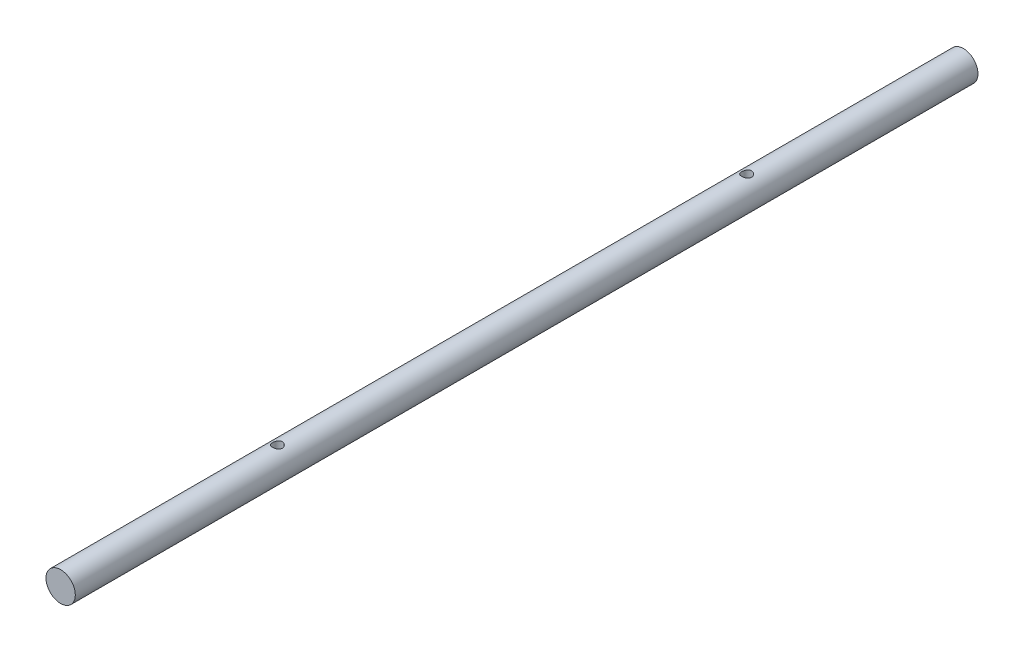
SolidWorks part; units mm, degrees
material "Plain Carbon Steel"
ref_plane "Front Plane" through (0, 0, 0) normal (0, 0, 1) x (1, 0, 0)
ref_plane "Top Plane" through (0, 0, 0) normal (0, 1, 0) x (1, 0, 0)
ref_plane "Right Plane" through (0, 0, 0) normal (1, 0, 0) x (0, 0, -1)
sketch "Sketch1" plane through (0, 0, 0) normal (0, 0, 1) x (1, 0, 0)
  circle A0 centre (0, 0) radius 9.525
  dimension "D1" = 19.05
extrude "Boss-Extrude1" add sketch "Sketch1" along normal blind 586.105
sketch3d "3DSketch1" plane through (0, 0, 0) normal (0, 0, 1) x (1, 0, 0)
ref_axis "Axis1" through (0, 0, 586.105) along (0, 0, -1)
ref_plane "Plane1" through (0, -9.525, 0) normal (0, 1, 0) x (1, 0, 0)
sketch "Sketch3" plane through (0, -9.525, 0) normal (0, 1, 0) x (1, 0, 0)
  line L0 (0, -586.105) -> (0, 0) construction
  line L1 (9.525, 0) -> (-9.525, 0) construction
  line L2 (-9.525, -586.105) -> (9.525, -586.105) construction
  circle A0 centre (0, -445.389) radius 3.175
  circle A1 centre (0, -140.716) radius 3.175
  dimension "D1" = 0
  dimension "D2" = 0
  dimension "D3" = 6.35
  dimension "D4" = 140.716
  dimension "D5" = 6.35
  dimension "D6" = 140.716
extrude "Cut-Extrude2" cut sketch "Sketch3" along normal up to next
sketch "Sketch5" plane through (0, -9.525, 0) normal (0, 1, 0) x (1, 0, 0)
  line L0 (0, -178.816) -> (0, -159.766) construction
  line L1 (-2.3813, -178.816) -> (-2.3813, -159.766)
  line L2 (2.3813, -178.816) -> (2.3813, -159.766)
  line L3 (0, -407.289) -> (0, -426.339) construction
  line L4 (2.3812, -407.289) -> (2.3812, -426.339)
  line L5 (-2.3813, -407.289) -> (-2.3813, -426.339)
  arc A0 (-2.3813, -178.816) -> (2.3813, -178.816) centre (0, -178.816) ccw
  arc A1 (2.3813, -159.766) -> (-2.3813, -159.766) centre (0, -159.766) ccw
  arc A2 (2.3812, -407.289) -> (-2.3813, -407.289) centre (0, -407.289) ccw
  arc A3 (-2.3813, -426.339) -> (2.3812, -426.339) centre (0, -426.339) ccw
  circle A6 centre (0, -140.716) radius 3.175 construction
  circle A7 centre (0, -445.389) radius 3.175 construction
  point P3 (0, -169.291)
  point P10 (0, -416.814)
  dimension "D1" = 2.3813
  dimension "D2" = 2.3813
  dimension "D3" = 19.05
  dimension "D4" = 19.05
  dimension "D5" = 19.05
  dimension "D6" = 19.05
extrude "Cut-Extrude3" cut sketch "Sketch5" along normal blind 2.3813
